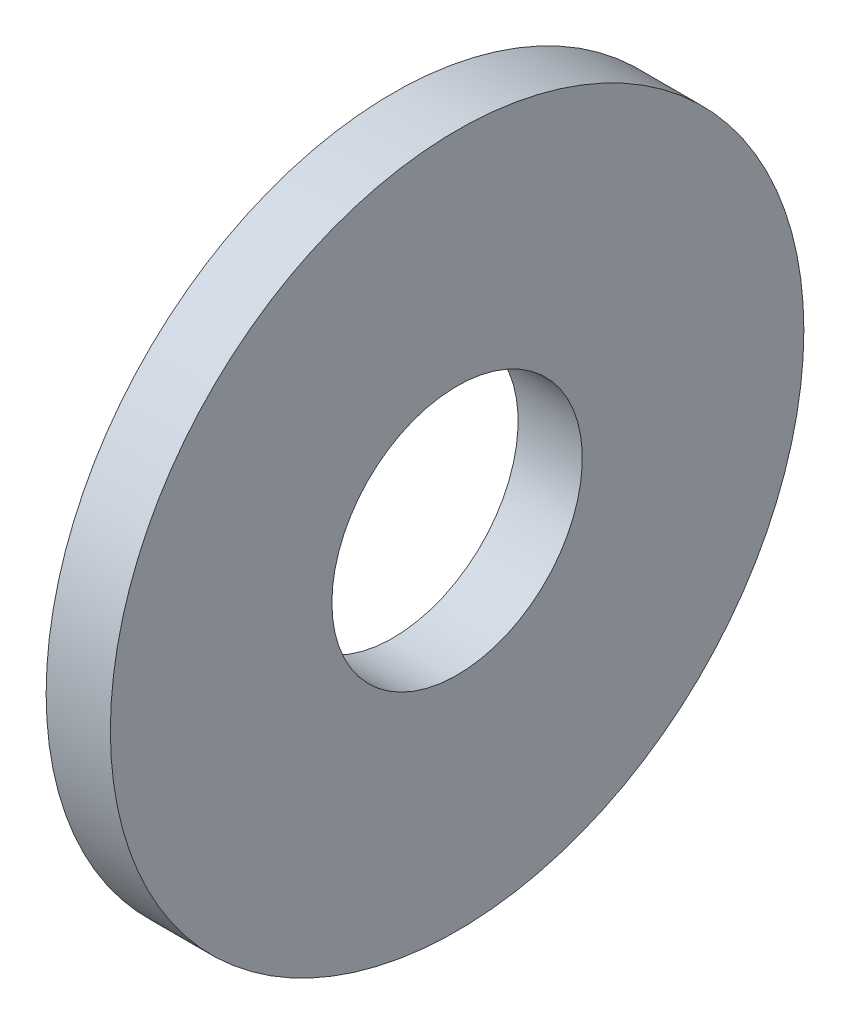
SolidWorks part; units mm, degrees
ref_plane "Plane1" through (0, 0, 0) normal (0, 0, 1) x (1, 0, 0)
ref_plane "Plane2" through (0, 0, 0) normal (0, 1, 0) x (1, 0, 0)
ref_plane "Plane3" through (0, 0, 0) normal (1, 0, 0) x (0, 0, -1)
sketch "Sketch1" plane through (0, 0, 0) normal (0, 0, 1) x (1, 0, 0)
  line L0 (-34.925, 0) -> (9.525, 0) construction
  line L1 (0, 19.5) -> (0, 54)
  line L2 (0, 54) -> (-10, 54)
  line L3 (-10, 54) -> (-10, 19.5)
  line L4 (-10, 19.5) -> (0, 19.5)
  dimension "Thickness" = 10
  dimension "Inside_dia" = 39
  dimension "Outside_dia" = 108
revolve "Base-Revolve" add sketch "Sketch1" angle 360 about L0
